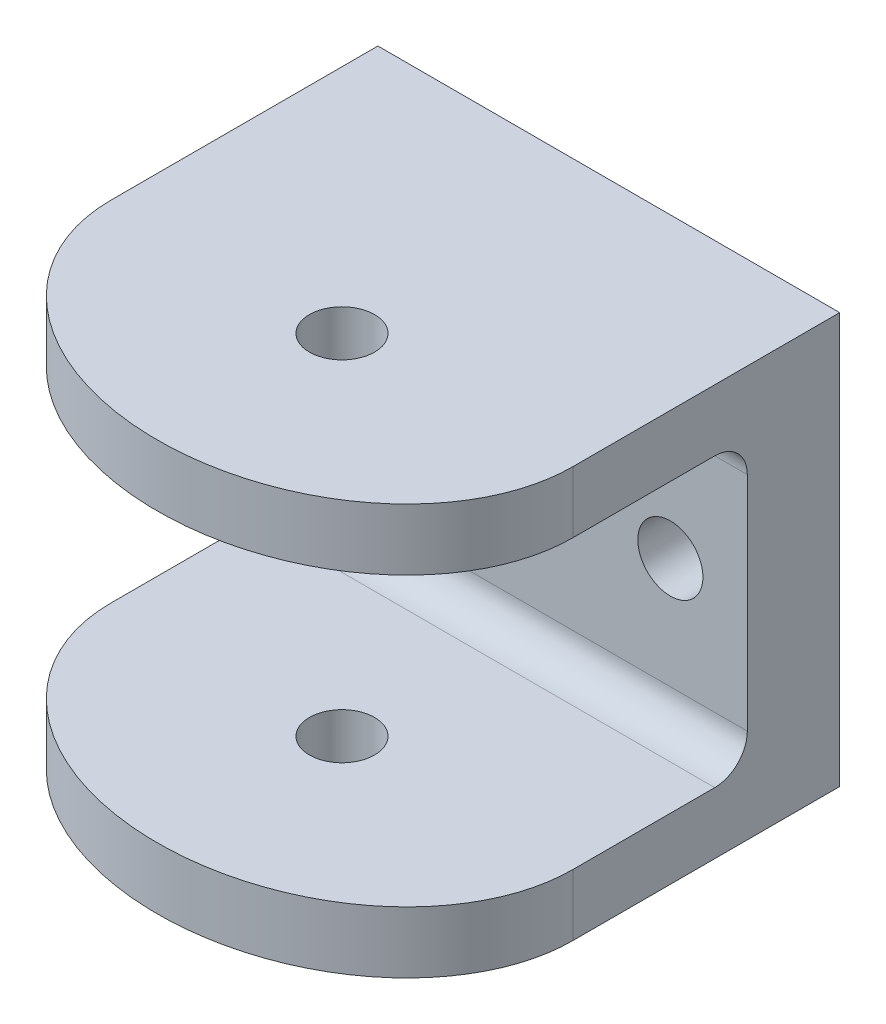
SolidWorks part; units mm, degrees
ref_plane "Front Plane" through (0, 0, 0) normal (0, 0, 1) x (1, 0, 0)
ref_plane "Top Plane" through (0, 0, 0) normal (0, 1, 0) x (1, 0, 0)
ref_plane "Right Plane" through (0, 0, 0) normal (1, 0, 0) x (0, 0, -1)
sketch "Sketch1" plane through (0, 0, 0) normal (0, 0, 1) x (1, 0, 0)
  line L0 (0, 0) -> (-15, 0) construction
  line L1 (-22.5, -20) -> (22.5, -20)
  line L2 (-22.5, -20) -> (-22.5, 20)
  line L3 (-22.5, 20) -> (22.5, 20)
  line L4 (22.5, -20) -> (22.5, 20)
  line L5 (-22.5, -20) -> (22.5, 20) construction
  line L6 (-22.5, 20) -> (22.5, -20) construction
  line L7 (0, 0) -> (15, 0) construction
  circle A0 centre (15, 0) radius 3.175
  circle A1 centre (-15, 0) radius 3.175
  point P0 (0, 0)
  dimension "D4" = 6.35
  dimension "D1" = 45
  dimension "D2" = 40
  dimension "D3" = 30
extrude "Boss-Extrude1" add sketch "Sketch1" along normal blind 9
sketch "Sketch2" plane through (0, 0, 9) normal (0, 0, 1) x (1, 0, 0)
  line L1 (-22.5, 20) -> (22.5, 20)
  line L2 (-22.5, 20) -> (-22.5, 14)
  line L3 (-22.5, 14) -> (22.5, 14)
  line L4 (22.5, -20) -> (22.5, 20)
  line L5 (22.5, 20) -> (-22.5, 20)
  line L6 (-22.5, 20) -> (-22.5, -20)
  line L7 (-22.5, -20) -> (22.5, -20)
  line L8 (22.5, -20) -> (22.5, 20) construction
  line L9 (22.5, 20) -> (-22.5, 20) construction
  line L10 (-22.5, 20) -> (-22.5, -20) construction
  line L11 (-22.5, -20) -> (22.5, -20) construction
  line L12 (22.5, 20) -> (22.5, 14)
  line L13 (22.5, -20) -> (-22.5, -20)
  line L14 (22.5, -20) -> (22.5, -14)
  line L15 (22.5, -14) -> (-22.5, -14)
  line L16 (-22.5, -20) -> (-22.5, -14)
  dimension "D2" = 6
  dimension "D3" = 6
  dimension "D1" = 0
extrude "Boss-Extrude2" add sketch "Sketch2" along normal blind 35
fillet "Fillet1" radius 3.175 2 edges at (0, 14, 9) (0, -14, 9)
sketch "Sketch3" plane through (0, 20, 0) normal (0, 1, 0) x (1, 0, 0)
  line L0 (22.5, -9) -> (-22.5, -9) construction
  line L1 (22.5, -9) -> (-22.5, -9) construction
  line L2 (22.5, -44) -> (22.5, 0) construction
  line L3 (22.5, -44) -> (22.5, -26)
  line L4 (-22.5, -44) -> (-22.5, 0) construction
  line L6 (-22.5, -44) -> (-22.5, -26)
  line L7 (22.5, -44) -> (-22.5, -44)
  line L8 (22.5, 0) -> (-22.5, 0) construction
  circle A0 centre (0, -26) radius 3.175
  ellipse E0 centre (0, -26) end of major axis (-22.5, -26) minor radius 18 (-22.5, -26) -> (7.3951, -9) ccw
  point P4 (0, -9)
  point P7 (0, 0)
  line M6 (-22.5, 0) -> (-22.5, -44)
  line M7 (-22.5, -44) -> (22.5, -44)
  line M8 (22.5, -44) -> (22.5, 0)
  dimension "D1" = 6.35
  dimension "D2" = 26
  dimension "D3" = 22.5
  dimension "D4" = 0
  dimension "D5" = 18
extrude "Cut-Extrude1" cut sketch "Sketch3" against normal through all contours M6 M7 | L7 M8 | A0 region at (17.4767, 20, 39.9774) region at (-17.4742, 20, 39.9794) region at (0, 20, 26)
ref_point "Point4"
ref_point "Point6"
ref_point "Point8"
ref_point "Point12"
sketch "Sketch4" plane through (0, 0, 0) normal (0, 1, 0) x (1, 0, 0)
  point P0 (0, -26)
